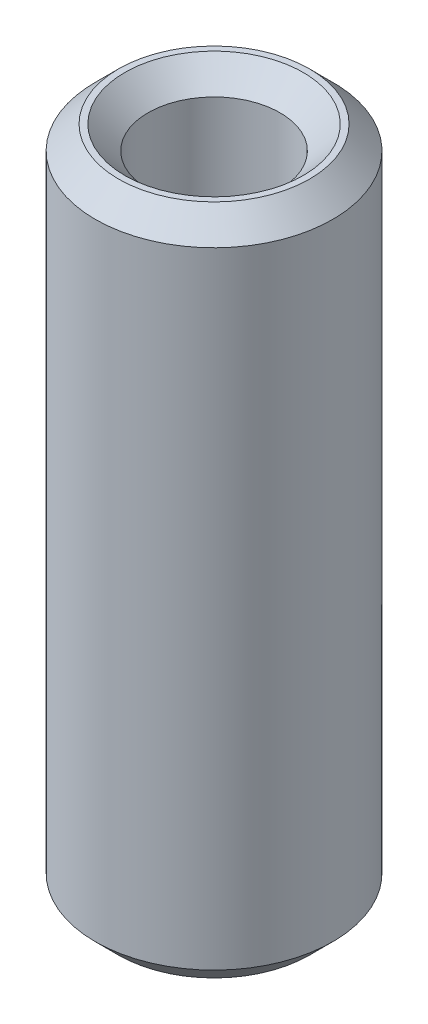
SolidWorks part; units mm, degrees
ref_plane "Front Plane" through (0, 0, 0) normal (0, 0, 1) x (1, 0, 0)
ref_plane "Top Plane" through (0, 0, 0) normal (0, 1, 0) x (1, 0, 0)
ref_plane "Right Plane" through (0, 0, 0) normal (1, 0, 0) x (0, 0, -1)
sketch "Sketch1" plane through (0, 0, 0) normal (0, 1, 0) x (1, 0, 0)
  circle A0 centre (0, 0) radius 12.5
  dimension "SLEEVE_OD" = 25
extrude "Boss-Extrude1" add sketch "Sketch1" along normal blind 70.7418
sketch "Sketch2" plane through (0, 0, 0) normal (0, 1, 0) x (1, 0, 0)
  circle A0 centre (0, 0) radius 6.9486
  dimension "BORE_D" = 13.8973
extrude "Cut-Extrude1" cut sketch "Sketch2" along normal through all
chamfer "Chamfer1" distance 2.4479 angle 45 4 edges at (0, 70.7418, 6.9486) (0, 0, 6.9486) (0, 0, 12.5) (0, 70.7418, 12.5)
